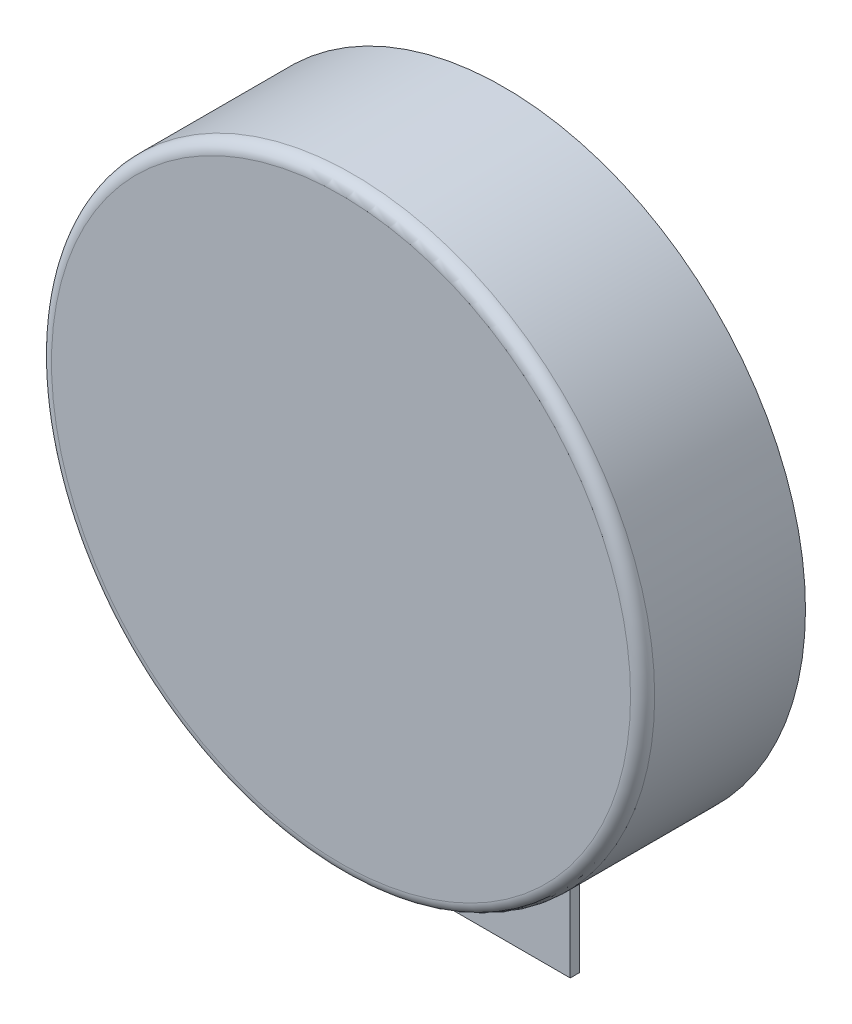
SolidWorks part; units mm, degrees
ref_plane "Front" through (0, 0, 0) normal (0, 0, 1) x (1, 0, 0)
ref_plane "Top" through (0, 0, 0) normal (0, 1, 0) x (1, 0, 0)
ref_plane "Right" through (0, 0, 0) normal (1, 0, 0) x (0, 0, -1)
sketch "Sketch1" plane through (0, 0, 0) normal (0, 0, 1) x (1, 0, 0)
  circle A0 centre (0, 0) radius 5
  dimension "D1" = 10
extrude "Boss-Extrude1" add sketch "Sketch1" along normal blind 2.7
sketch "Sketch2" plane through (0, 0, 0) normal (0, 0, -1) x (-1, 0, 0)
  line L0 (0, -5.7832) -> (0, 5.8717) construction
sketch "Sketch3" plane through (0, 0, 0) normal (0, 0, -1) x (-1, 0, 0)
  line L0 (1.25, -4.8412) -> (1.25, -7.0912)
  line L1 (-1.25, -4.8412) -> (-1.25, -7.0912)
  line L2 (0, -5.7832) -> (0, 5.8717) construction
  line L3 (1.25, -7.0912) -> (-1.25, -7.0912)
  line L4 (1.25, -4.8412) -> (1.25, -4.1797)
  line L5 (1.25, -4.1797) -> (-1.25, -4.1797)
  line L6 (-1.25, -4.1797) -> (-1.25, -4.8412)
  dimension "D2" = 1.25
  dimension "D3" = 1.25
  dimension "D4" = 2.25
extrude "Boss-Extrude2" add sketch "Sketch3" against normal blind 0.15
sketch "Sketch4" plane through (0, -7.0912, 0) normal (0, -1, 0) x (1, 0, 0)
  line L0 (1.25, 0) -> (-1.25, 0) construction
  circle A0 centre (-0.625, 0.101) radius 0.101
  circle A1 centre (0.625, 0.101) radius 0.101
  dimension "D1" = 0.202
  dimension "D2" = 0.202
  dimension "D3" = 0.625
  dimension "D4" = 0.625
  dimension "D5" = 0.101
  dimension "D6" = 0.101
extrude "Boss-Extrude3" [suppressed] add sketch "Sketch4" along normal blind 3.9 and the other way blind 2.2 separate body
fillet "Fillet1" [suppressed] radius 0.2
fillet "Fillet2" radius 0.2 1 edges at (5, 0, 2.7)
sketch "Sketch5" [suppressed] plane through (0, -10.9912, 0) normal (0, -1, 0) x (1, 0, 0)
  circle A1 centre (-0.625, 0.101) radius 0.075
  circle A2 centre (0.625, 0.101) radius 0.075
  dimension "D1" = 0.15
  dimension "D2" = 0.15
extrude "Cut-Extrude4" [suppressed] cut sketch "Sketch5" against normal blind 0.25 flip side to cut
